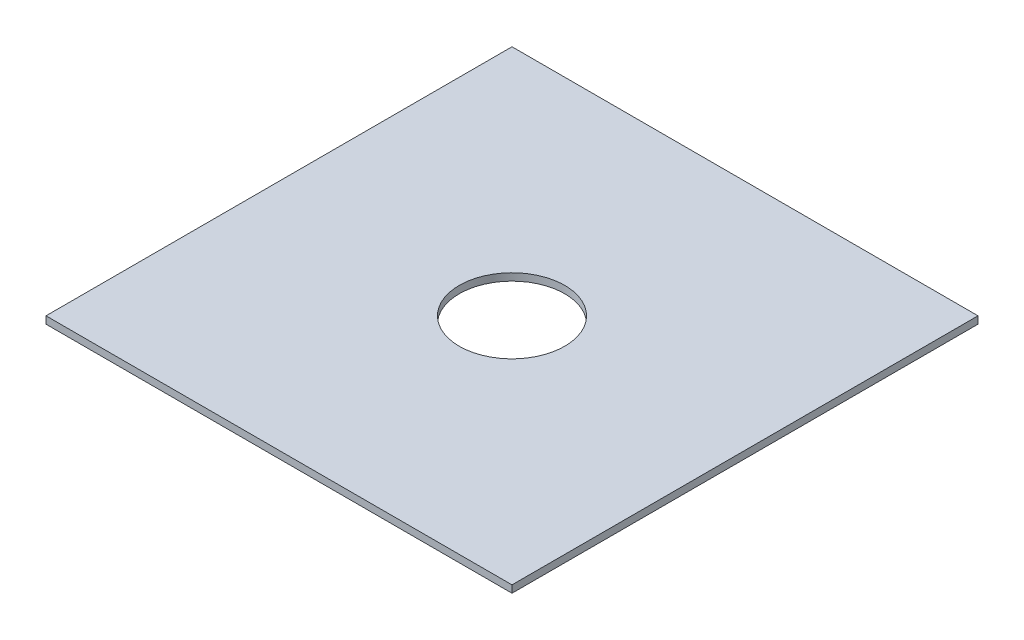
SolidWorks part; units mm, degrees
material "Acrylic (Medium-high impact)"
ref_plane "Front" through (0, 0, 0) normal (0, 0, 1) x (1, 0, 0)
ref_plane "Top" through (0, 0, 0) normal (0, 1, 0) x (1, 0, 0)
ref_plane "Right" through (0, 0, 0) normal (1, 0, 0) x (0, 0, -1)
sketch "Sketch1" plane through (0, 0, 0) normal (0, 1, 0) x (1, 0, 0)
  line L1 (-203.2, 406.4) -> (203.2, 406.4)
  line L2 (-203.2, 406.4) -> (-203.2, 0)
  line L3 (-203.2, 0) -> (203.2, 0)
  line L4 (203.2, 406.4) -> (203.2, 0)
  point P4 (0, 0)
  dimension "D1" = 406.4
  dimension "D2" = 406.4
extrude "Boss-Extrude1" add sketch "Sketch1" along normal blind 6.35
sketch "Sketch2" plane through (0, 6.35, 0) normal (0, 1, 0) x (1, 0, 0)
  line L0 (203.2, 0) -> (203.2, 406.4) construction
  circle A0 centre (0, 203.2) radius 46
  point P2 (0, 0)
  point P4 (0, 0)
  point P5 (0, 0)
  point P8 (203.2, 203.2)
  dimension "D1" = 92
extrude "Cut-Extrude1" cut sketch "Sketch2" against normal up to next
